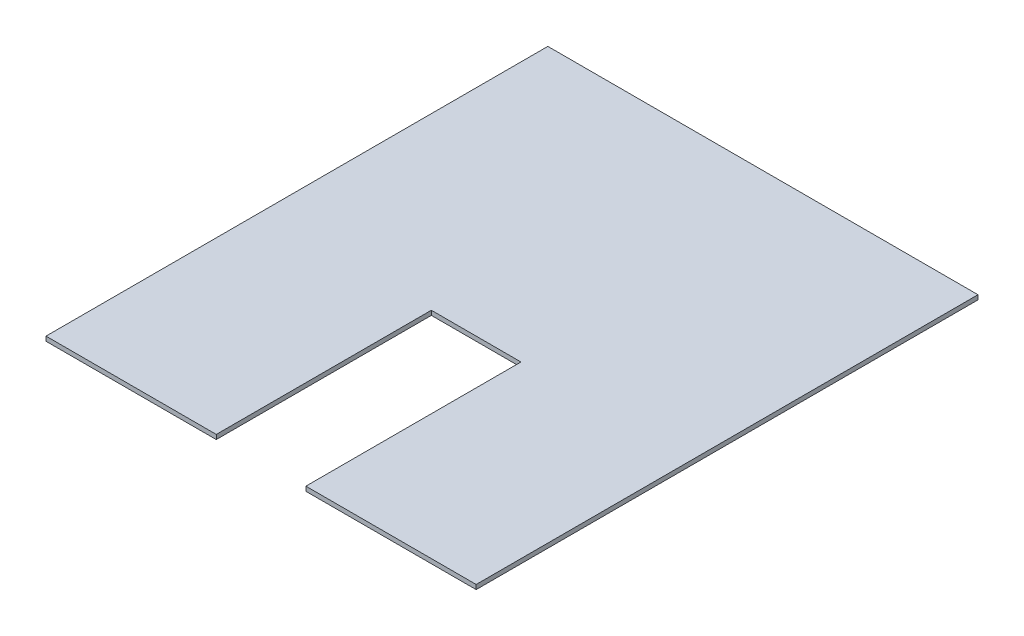
SolidWorks part; units mm, degrees
ref_plane "Front Plane" through (0, 0, 0) normal (0, 0, 1) x (1, 0, 0)
ref_plane "Top Plane" through (0, 0, 0) normal (0, 1, 0) x (1, 0, 0)
ref_plane "Right Plane" through (0, 0, 0) normal (1, 0, 0) x (0, 0, -1)
sketch "Sketch1" plane through (0, 0, 0) normal (0, 1, 0) x (1, 0, 0)
  line L1 (-152.4, -177.8) -> (152.4, -177.8)
  line L2 (-152.4, -177.8) -> (-152.4, 177.8)
  line L3 (-152.4, 177.8) -> (152.4, 177.8)
  line L4 (152.4, -177.8) -> (152.4, 177.8)
  line L5 (-152.4, -177.8) -> (152.4, 177.8) construction
  line L6 (-152.4, 177.8) -> (152.4, -177.8) construction
  point P0 (0, 0)
  dimension "D1" = 355.6
  dimension "D2" = 304.8
extrude "Boss-Extrude1" add sketch "Sketch1" along normal blind 3.175
sketch "Sketch2" plane through (0, 3.175, 0) normal (0, 1, 0) x (1, 0, 0)
  line L0 (-152.4, -177.8) -> (152.4, -177.8) construction
  line L1 (-31.75, -25.4) -> (31.75, -25.4)
  line L2 (-31.75, -25.4) -> (-31.75, -177.8)
  line L3 (-31.75, -177.8) -> (31.75, -177.8)
  line L4 (31.75, -25.4) -> (31.75, -177.8)
  line L5 (-31.75, -25.4) -> (31.75, -177.8) construction
  line L6 (-31.75, -177.8) -> (31.75, -25.4) construction
  point P0 (0, -101.6)
  dimension "D1" = 152.4
  dimension "D2" = 63.5
extrude "Cut-Extrude1" cut sketch "Sketch2" against normal blind 3.175
